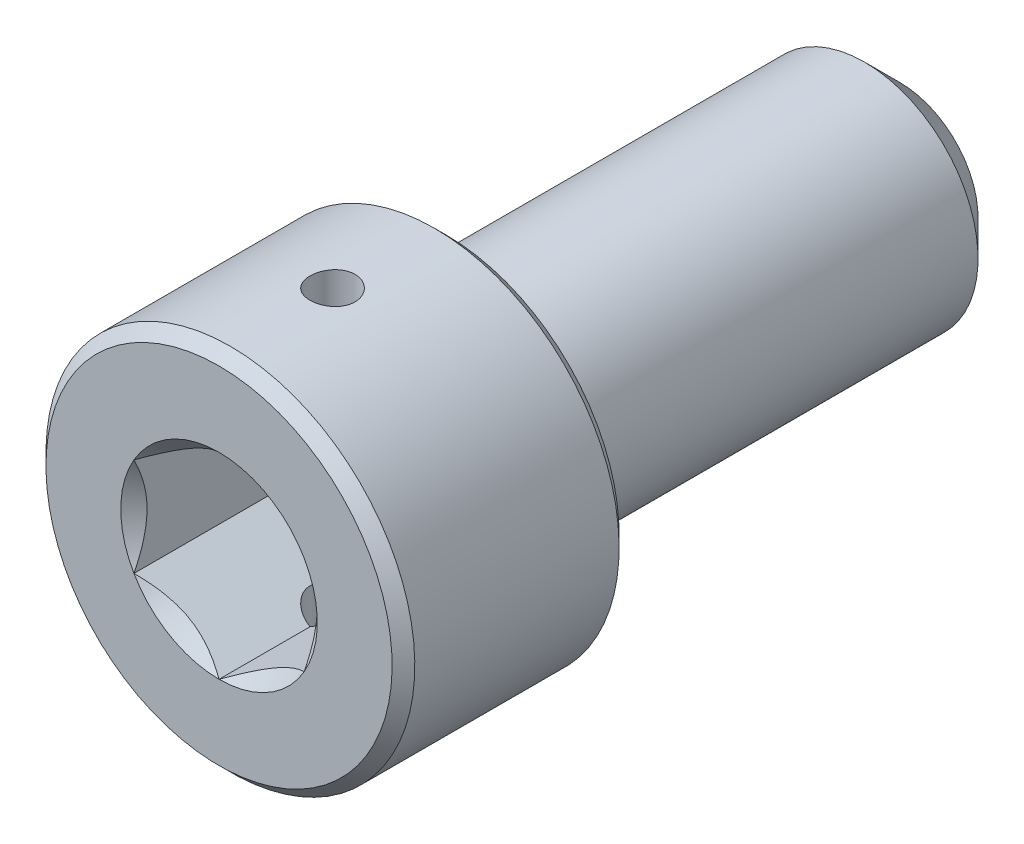
SolidWorks part; units mm, degrees
ref_plane "Front Plane" through (0, 0, 0) normal (0, 0, 1) x (1, 0, 0)
ref_plane "Top Plane" through (0, 0, 0) normal (0, 1, 0) x (1, 0, 0)
ref_plane "Right Plane" through (0, 0, 0) normal (1, 0, 0) x (0, 0, -1)
sketch "Sketch1" plane through (0, 0, 0) normal (1, 0, 0) x (0, 0, -1)
  line L0 (-12, 0) -> (12, 0) construction
  line L1 (12, 0) -> (12, 2.75) construction
  line L2 (12, 2.75) -> (10.75, 4) construction
  line L3 (10.75, 4) -> (11.0625, 4) construction
  line L4 (11.0625, 4) -> (-4, 4) construction
  line L5 (-4, 4) -> (-4, 6.5) construction
  line L6 (-4, 6.5) -> (-12, 6.5) construction
  line L7 (-12, 6.5) -> (-12, 0) construction
  line L8 (12, 2.75) -> (12, 4) construction
  line L9 (11.9219, 4.1353) -> (12.5469, 3.0528) construction
  line L10 (12.5469, 3.0528) -> (13.1719, 4.1353) construction
  line L11 (13.1719, 4.1353) -> (11.9219, 4.1353) construction
  line L12 (12.5469, 4.1353) -> (12.5469, 4) construction
  line L13 (12.5469, 3.0528) -> (12.5469, 3.1881) construction
  line L14 (12.4687, 3.1881) -> (12.625, 3.1881) construction
  line L15 (12, 4) -> (13.0938, 4) construction
  line L16 (11.9609, 4.0677) -> (13.1328, 4.0677) construction
  line L17 (12, 0) -> (12, -4) construction
  line L18 (-4.4, 6.5) -> (-4, 6.1) construction
  line L19 (-11.6, 6.5) -> (-12, 6.1) construction
  line L20 (-4, 4) -> (-4, 0) construction
  line L21 (-4, 2) -> (1.3333, 2) construction
  line L22 (1.3333, 2) -> (6.6667, 2) construction
  line L23 (6.6667, 2) -> (12, 2) construction
  line L24 (1.3333, 2) -> (1.3333, 4) construction
  line L25 (1.3333, 4) -> (1.3333, 6.5) construction
  line L26 (6.6667, 2) -> (6.6667, 6.5) construction
  point P0 (-12, 3)
  point P3 (8.875, 4)
  point P4 (0, 0)
  point P18 (6.6667, 4)
  point P22 (12.5469, 3.1881)
  point P24 (11.0625, 4)
  point P25 (12.5469, 4)
  point P28 (12.5469, 4.0677)
  point P29 (8.875, -4)
  point P30 (1.3333, 4)
  point P31 (-8, 6.5)
  point P37 (-5.4, 6.5)
  point P38 (-11.4, 6.5)
  point P45 (1.3333, 2)
  point P46 (6.6667, 2)
  dimension "D1" = 45
  dimension "D2" = 0.1562
  dimension "D3" = 1.25
  dimension "D7" = 0.4
  dimension "D8" = 0.4
  dimension "D9" = 0.4
  dimension "D10" = 0.2
  dimension "D11" = 1
  dimension "Drive Size" = 6
  dimension "Head Diameter" = 13
  dimension "Head Height" = 8
  dimension "Thread Pitch" = 1.25
  dimension "Thread Major Diameter" = 8
  dimension "Length" = 16
  dimension "D12" = 0.9375
  dimension "D4" = 3.125
sketch "Sketch2" plane through (0, 0, 0) normal (1, 0, 0) x (0, 0, -1)
  line L0 (-12, 0) -> (-12, 6.1)
  line L1 (-11.6, 6.5) -> (-4.4, 6.5)
  line L2 (-4, 6.1) -> (-4, 4)
  line L3 (-4, 4) -> (10.75, 4)
  line L4 (10.75, 4) -> (12, 2.75)
  line L5 (12, 2.75) -> (12, 0)
  line L6 (-4.4, 6.5) -> (-4, 6.1) construction
  line L7 (12, 0) -> (-12, 0)
  line L8 (-11.6, 6.5) -> (-12, 6.1) construction
  line L9 (-4.4, 6.5) -> (-4, 6.1)
  line L10 (-11.6, 6.5) -> (-12, 6.1)
revolve "Revolve1" add sketch "Sketch2" angle 360 about L7
sketch "Sketch3" plane through (0, 0, 12) normal (0, 0, 1) x (1, 0, 0)
  line L1 (3, -1.7321) -> (3, 1.7321)
  line L2 (3, 1.7321) -> (0, 3.4641)
  line L3 (0, 3.4641) -> (-3, 1.7321)
  line L4 (-3, 1.7321) -> (-3, -1.7321)
  line L5 (-3, -1.7321) -> (0, -3.4641)
  line L6 (0, -3.4641) -> (3, -1.7321)
  circle A0 centre (0, 0) radius 3 construction
extrude "Cut-Extrude1" cut sketch "Sketch3" against normal offset from surface (7 mm away) 1 up to face at (0, 6.1, 4)
sketch "Sketch4" plane through (0, 0, 12) normal (0, 0, 1) x (1, 0, 0)
  circle A0 centre (0, 0) radius 3.4641
extrude "Cut-Extrude2" cut sketch "Sketch4" against normal up to vertex (4 mm away) draft 45 up to point (0, 6.5, 8)
ref_plane "Plane1" [suppressed] through (0, 0, -11.0625) normal (0, 0, 1) x (1, 0, 0)
split "Split1" [suppressed] bodies to split 106
sketch "Sketch6" [suppressed] plane through (0, 0, -12) normal (0, 0, -1) x (-1, 0, 0)
  circle A0 centre (0, 0) radius 4
curve "Helix/Spiral1" [suppressed] pitch 1.25 height 17.4375 turns 13.95
sketch "Sketch7" [suppressed] plane through (0, 0, 0) normal (1, 0, 0) x (0, 0, -1)
  line L0 (11.9609, 4.0677) -> (13.1328, 4.0677)
  line L1 (13.1328, 4.0677) -> (12.625, 3.1881)
  line L2 (12.625, 3.1881) -> (12.4687, 3.1881)
  line L3 (12.4687, 3.1881) -> (11.9609, 4.0677)
sweep "Cut-Sweep1" [suppressed] cut profiles "Sketch7" path "Helix/Spiral1"
sketch "Sketch8" [suppressed] plane through (0, 0, 4) normal (0, 0, -1) x (-1, 0, 0)
  circle A0 centre (0, 0) radius 4
extrude "Boss-Extrude1" [suppressed] add sketch "Sketch8" along normal through all draft 45
sketch "Sketch9" plane through (0, 0, 0) normal (0, 1, 0) x (1, 0, 0)
  line L0 (0, -4) -> (0, -12) construction
  line L1 (6.1, -4) -> (-6.1, -4) construction
  circle A0 centre (0, -8) radius 0.7938
  dimension "D1" = 1.5875
extrude "Cut-Extrude3" cut sketch "Sketch9" against normal blind 7 and the other way blind 7 contours A0
equation "\"D2@Sketch1\" = \"Thread Pitch@Sketch1\" / 8"
equation "\"D3@Sketch1\"= \"Thread Pitch@Sketch1\""
equation "\"D4@Helix/Spiral1\" = \"Thread Pitch@Sketch1\""
equation "\"D7@Sketch1\" = \"Head Height@Sketch1\" * .05"
equation "\"D8@Sketch1\"=\"D7@Sketch1\""
equation "\"D9@Sketch1\"=\"D7@Sketch1\""
equation "\"D10@Sketch1\"=\"D7@Sketch1\"/2"
equation "\"D11@Sketch1\"=\"D10@Sketch1\"*5"
equation "\"D4@Sketch1\"=\"Thread Pitch@Sketch1\"*2.5"
equation "\"D12@Sketch1\"=\"Thread Pitch@Sketch1\"*.75"
